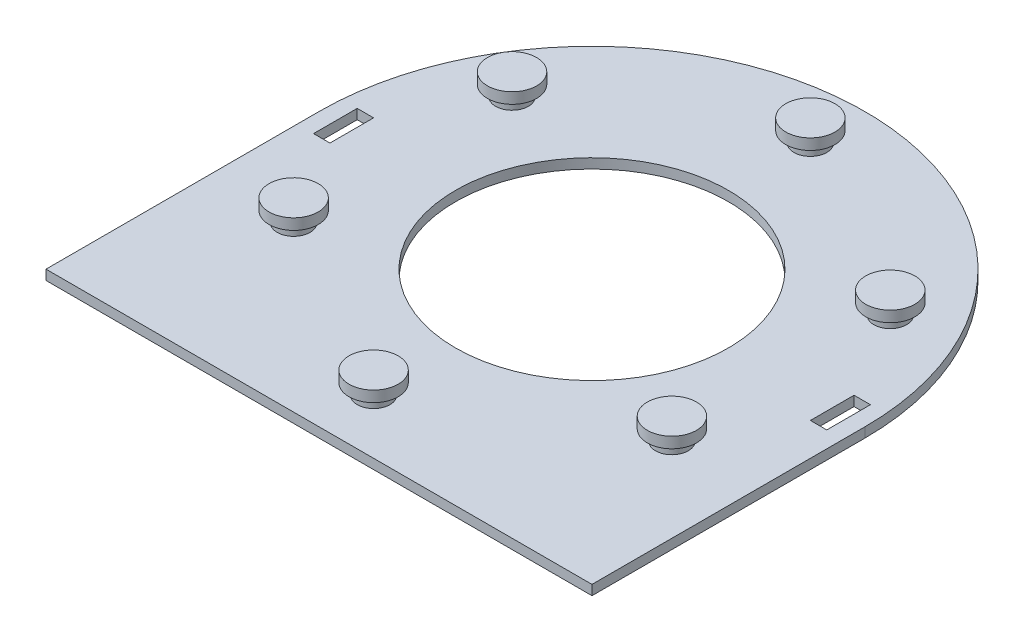
SolidWorks part; units mm, degrees
ref_plane "Front Plane" through (0, 0, 0) normal (0, 0, 1) x (1, 0, 0)
ref_plane "Top Plane" through (0, 0, 0) normal (0, 1, 0) x (1, 0, 0)
ref_plane "Right Plane" through (0, 0, 0) normal (1, 0, 0) x (0, 0, -1)
sketch "Sketch1" plane through (0, 0, 0) normal (0, 1, 0) x (1, 0, 0)
  line L0 (-50, 0) -> (-50, -50)
  line L1 (-50, -50) -> (50, -50)
  line L2 (0, -50) -> (0, 58.2831) construction
  line L3 (50, 0) -> (50, -50)
  arc A2 (50, 0) -> (-50, 0) centre (0, 0) ccw
  point P7 (0, 58.2831)
  dimension "D1" = 50
extrude "Boss-Extrude1" add sketch "Sketch1" along normal blind 1.8 contours A2 L0 L1 L3
sketch "Sketch2" plane through (0, 1.8, 0) normal (0, 1, 0) x (1, 0, 0)
  line L0 (0, 50) -> (0, -50) construction
  line L1 (-50, 0) -> (50, 0) construction
  circle A1 centre (0, -40) radius 4.5
  circle A2 centre (0, 0) radius 40 construction
  circle A3 centre (0, 0) radius 25
  circle A4 centre (0, -40) radius 3
  dimension "D1" = 80
  dimension "D2" = 50
  dimension "D3" = 9
  dimension "D4" = 6
extrude "Cut-Extrude1" cut sketch "Sketch2" against normal up to surface (1.8 mm away) contours A3 up to face at (0, 0, 12.5)
extrude "Boss-Extrude2" add sketch "Sketch2<3>" along normal blind 4 contours A1
sketch "Sketch2<3>" plane through (0, 1.8, 0) normal (0, 1, 0) x (1, 0, 0) same geometry as "Sketch2"
extrude "Cut-Extrude2" cut sketch "Sketch2<4>" along normal blind 2 contours A4 | A1
sketch "Sketch2<4>" plane through (0, 1.8, 0) normal (0, 1, 0) x (1, 0, 0) same geometry as "Sketch2"
pattern_circular "CirPattern1" count 12 every 30 about axis through (0, -70.7107, 0) along (0, 1, 0) skipping 1, 3, 5, 7, 9, 11 of "Boss-Extrude2", "Cut-Extrude2"
sketch "Sketch4" plane through (0, 1.8, 0) normal (0, 1, 0) x (1, 0, 0)
  line L0 (0, 50) -> (0, -50) construction
  line L1 (-50, 0) -> (50, 0) construction
sketch "Sketch5" plane through (0, 1.8, 0) normal (0, 1, 0) x (1, 0, 0)
  line L0 (0, 0) -> (0, 12.9279) construction
  line L1 (-47, 4) -> (-44, 4)
  line L2 (-47, 4) -> (-47, -4)
  line L3 (-47, -4) -> (-44, -4)
  line L4 (-44, 4) -> (-44, -4)
  line L5 (47, -4) -> (44, -4)
  line L6 (44, 4) -> (44, -4)
  line L7 (47, 4) -> (44, 4)
  line L8 (47, 4) -> (47, -4)
  point P4 (-44, 0)
  dimension "D1" = 8
  dimension "D2" = 3
  dimension "D3" = 3
extrude "Cut-Extrude3" cut sketch "Sketch5" against normal up to surface (1.8 mm away) up to face at (0, 0, 25)
